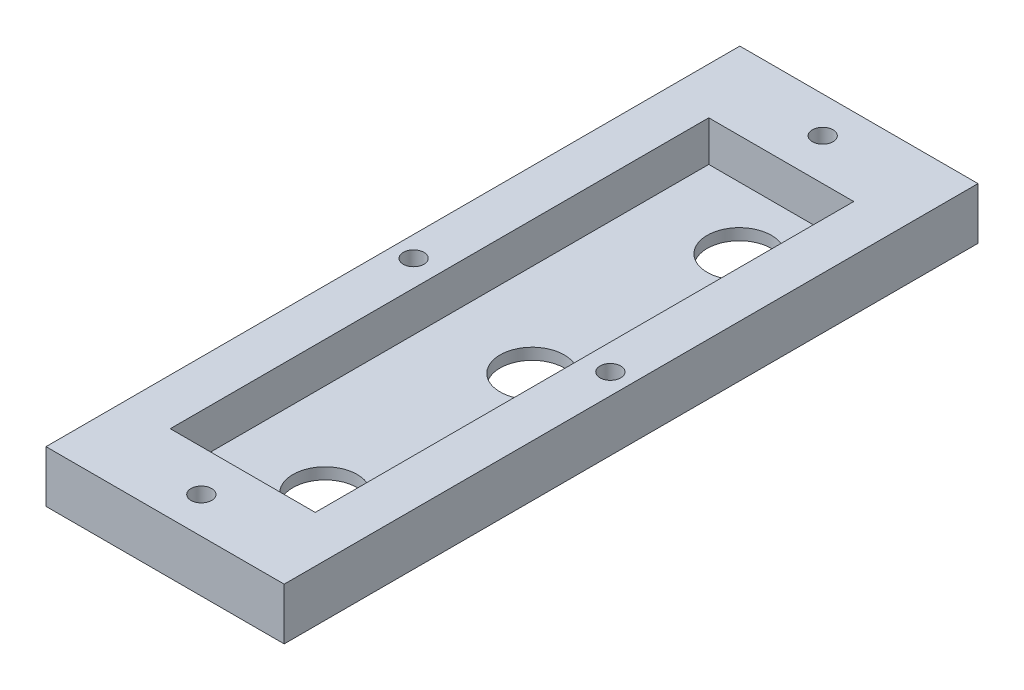
SolidWorks part; units mm, degrees
ref_plane "前视基准面" through (0, 0, 0) normal (0, 0, 1) x (1, 0, 0)
ref_plane "上视基准面" through (0, 0, 0) normal (0, 1, 0) x (1, 0, 0)
ref_plane "右视基准面" through (0, 0, 0) normal (1, 0, 0) x (0, 0, -1)
other "Configuration Table"
sketch "草图1" plane through (0, 0, 0) normal (0, 1, 0) x (1, 0, 0)
  line L5 (-11.5, -33.5) -> (11.5, -33.5)
  line L6 (-11.5, -33.5) -> (-11.5, 33.5)
  line L15 (-11.5, 33.5) -> (11.5, 33.5)
  line L16 (11.5, -33.5) -> (11.5, 33.5)
  line L17 (-11.5, -33.5) -> (11.5, 33.5) construction
  line L18 (-11.5, 33.5) -> (11.5, -33.5) construction
  point P0 (0, 0)
  dimension "D1" = 23
  dimension "D2" = 67
extrude "凸台-拉伸1" add sketch "草图1" along normal blind 1.1
sketch "草图2" plane through (0, 0, 0) normal (0, -1, 0) x (-1, 0, 0)
  line L0 (-1.95, 20) -> (-1.95, 0) construction
  line L1 (-1.95, 0) -> (-1.95, -20) construction
  circle A0 centre (-1.95, -20) radius 3.1
  circle A1 centre (-1.95, 0) radius 3.1
  circle A2 centre (-1.95, 20) radius 3.1
  dimension "D1" = 6.2
extrude "切除-拉伸1" cut sketch "草图2" against normal through all
sketch "草图3" plane through (0, 1.1, 0) normal (0, 1, 0) x (1, 0, 0)
  line L0 (11.5, 33.5) -> (-11.5, 33.5) construction
  line L1 (-7, 26) -> (7, 26)
  line L2 (-7, 26) -> (-7, -26)
  line L3 (-7, -26) -> (7, -26)
  line L4 (7, 26) -> (7, -26)
  line L5 (-11.5, 33.5) -> (-11.5, -33.5) construction
  line L6 (11.5, -33.5) -> (11.5, 33.5) construction
  line L7 (-11.5, -33.5) -> (11.5, -33.5) construction
  line M8 (11.5, -33.5) -> (11.5, 33.5)
  line M9 (11.5, 33.5) -> (-11.5, 33.5)
  line M10 (-11.5, 33.5) -> (-11.5, -33.5)
  line M11 (-11.5, -33.5) -> (11.5, -33.5)
  dimension "D1" = 7.5
  dimension "D2" = 4.5
  dimension "D3" = 4.5
  dimension "D4" = 7.5
extrude "凸台-拉伸2" add sketch "草图3" along normal blind 3.9 contours L1 L4 L3 L2 M11 M8 M9 M10 region at (0, 1.1, 32.7916)
sketch "草图4" plane through (0, 0, 0) normal (0, -1, 0) x (1, 0, 0)
  circle A0 centre (0, 30) radius 1
  circle A1 centre (0, 30) radius 1.5
  circle A2 centre (-9.5, 0) radius 1.5
  circle A3 centre (-9.5, 0) radius 1
  circle A4 centre (9.5, 0) radius 1.5
  circle A5 centre (9.5, 0) radius 1
  circle A6 centre (0, -30) radius 1.5
  circle A7 centre (0, -30) radius 1
  dimension "D1" = 2
  dimension "D2" = 3
extrude "切除-拉伸2" cut sketch "草图4" against normal offset from surface (3 mm away) 2 up to face at (0, 5, 0)
extrude "切除-拉伸3" cut sketch "草图4<2>" against normal through all contours A3 | A5 | A0 | A7 region at (-9.5, 0, 0) region at (9.5, 0, 0)
sketch "草图4<2>" plane through (0, 0, 0) normal (0, -1, 0) x (1, 0, 0) same geometry as "草图4"
